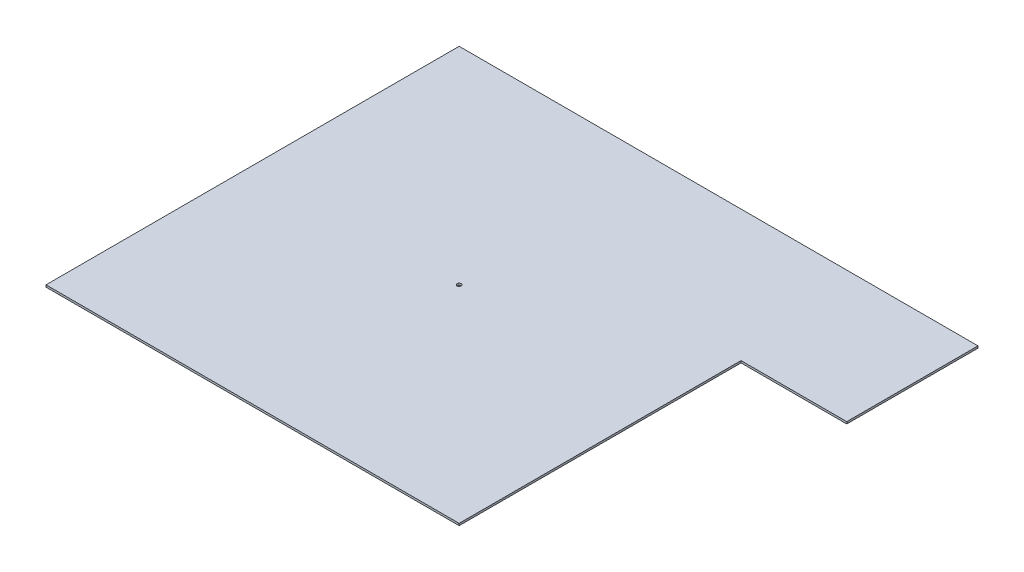
SolidWorks part; units mm, degrees
ref_plane "Front" through (0, 0, 0) normal (0, 0, 1) x (1, 0, 0)
ref_plane "Top" through (0, 0, 0) normal (0, 1, 0) x (1, 0, 0)
ref_plane "Right" through (0, 0, 0) normal (1, 0, 0) x (0, 0, -1)
sketch "Sketch1" plane through (0, 0, 0) normal (0, 1, 0) x (1, 0, 0)
  line L1 (-2568.575, -2568.575) -> (2568.575, -2568.575)
  line L2 (-2568.575, -2568.575) -> (-2568.575, 2568.575)
  line L3 (-2568.575, 2568.575) -> (2568.575, 2568.575)
  line L4 (2568.575, -2568.575) -> (2568.575, 2568.575)
  line L5 (-2568.575, -2568.575) -> (2568.575, 2568.575) construction
  line L6 (-2568.575, 2568.575) -> (2568.575, -2568.575) construction
  point P0 (0, 0)
  dimension "D1" = 5137.15
  dimension "D2" = 5137.15
extrude "Boss-Extrude1" add sketch "Sketch1" along normal blind 25.4
sketch "Sketch2" plane through (0, 0, 0) normal (0, -1, 0) x (1, 0, 0)
  circle A0 centre (0, 0) radius 25.4
  dimension "D1" = 50.8
extrude "Cut-Extrude1" cut sketch "Sketch2" against normal through all
sketch "Sketch3" plane through (0, 0, 0) normal (0, -1, 0) x (1, 0, 0)
  line L0 (2568.575, -2568.575) -> (3883.025, -2568.575)
  line L1 (3883.025, -2568.575) -> (3883.025, -936.625)
  line L2 (3883.025, -2568.575) -> (3883.025, -936.625) construction
  line L3 (3883.025, -936.625) -> (2568.575, -936.625)
  line L4 (2568.575, 2568.575) -> (2568.575, -2568.575) construction
  line L5 (3883.025, -936.625) -> (2568.575, -936.625) construction
  line L6 (2568.575, -936.625) -> (2568.575, -2568.575)
extrude "Boss-Extrude2" add sketch "Sketch3" against normal up to surface (25.4 mm away) up to face at (0, 25.4, -25.4)
